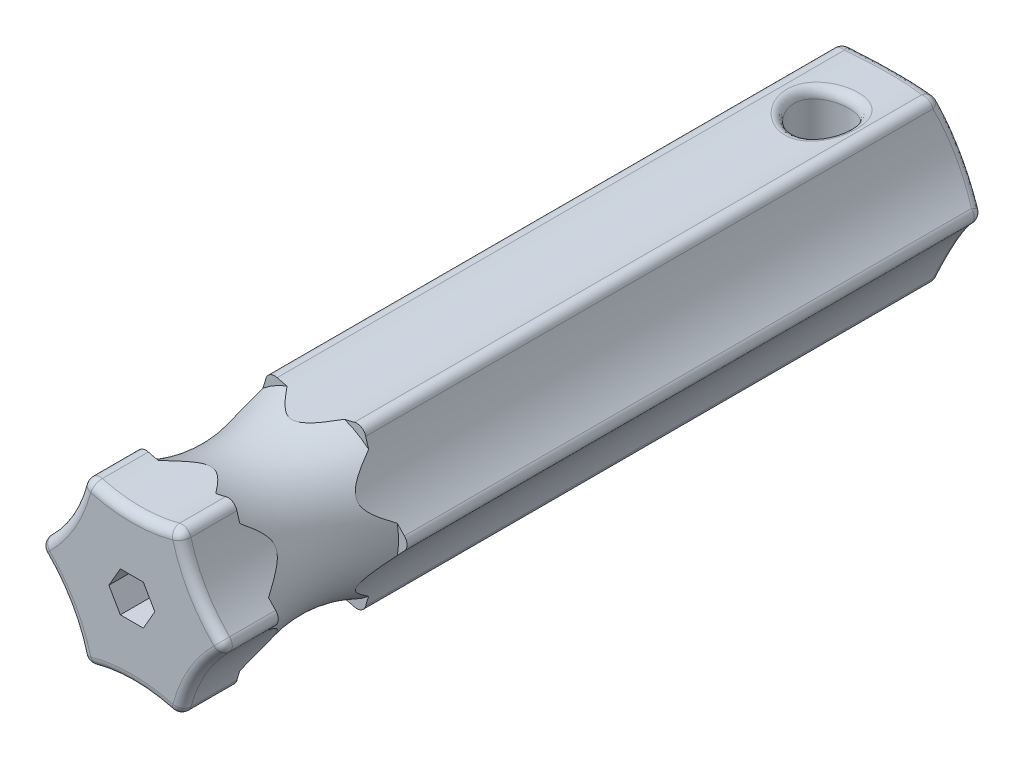
SolidWorks part; units mm, degrees
ref_plane "Alzado" through (0, 0, 0) normal (0, 0, 1) x (1, 0, 0)
ref_plane "Planta" through (0, 0, 0) normal (0, 1, 0) x (1, 0, 0)
ref_plane "Vista lateral" through (0, 0, 0) normal (1, 0, 0) x (0, 0, -1)
sketch "Croquis1" plane through (0, 0, 0) normal (0, 0, 1) x (1, 0, 0)
  line L1 (10.3923, 0) -> (5.1962, 9)
  line L2 (5.1962, 9) -> (-5.1962, 9)
  line L3 (-5.1962, 9) -> (-10.3923, 0)
  line L4 (-10.3923, 0) -> (-5.1962, -9)
  line L5 (-5.1962, -9) -> (5.1962, -9)
  line L6 (5.1962, -9) -> (10.3923, 0)
  circle A0 centre (0, 0) radius 9 construction
  dimension "D1" = 18
extrude "Saliente-Extruir1" add sketch "Croquis1" along normal blind 85
sketch "Croquis2" plane through (0, 0, 0) normal (1, 0, 0) x (0, 0, -1)
  line L0 (-85, -9) -> (0, -9) construction
  line L1 (0, 0) -> (-120.6116, 0) construction
  line L4 (-79, -9) -> (-79, -10.447)
  line L5 (-79, -10.447) -> (-65, -10.447)
  line L6 (-65, -10.447) -> (-65, -9)
  arc A0 (-79, -9) -> (-65, -9) centre (-72, -25.5831) cw
  dimension "D3" = 18
  dimension "D1" = 6
  dimension "D2" = 14
revolve "Cortar-Revolución2" cut sketch "Croquis2" angle 360 about L1
sketch "Croquis3" plane through (0, 0, 0) normal (0, 1, 0) x (1, 0, 0)
  line L2 (0, -0.25) -> (0, 21.7171) construction
  line L3 (-10.3923, -65) -> (-10.3923, 0) construction
  line L5 (0, -0.25) -> (0, 1.427)
  line L6 (0, 1.427) -> (-11.7694, 1.8249)
  arc A0 (0, -0.25) -> (-10.3923, -3) centre (-0.2681, -20.2482) ccw
  arc A1 (-10.3923, -3) -> (-11.7694, 1.8249) centre (137.6107, 41.8508) cw
  dimension "D2" = 20
  dimension "D1" = 3
  dimension "D3" = 0.25
revolve "Cortar-Revolución4" cut sketch "Croquis3" angle 360 about L2
sketch "Croquis4" plane through (0, 0, 85) normal (0, 0, 1) x (1, 0, 0)
  line L1 (2.5, 0) -> (1.25, 2.1651)
  line L2 (1.25, 2.1651) -> (-1.25, 2.1651)
  line L3 (-1.25, 2.1651) -> (-2.5, 0)
  line L4 (-2.5, 0) -> (-1.25, -2.1651)
  line L5 (-1.25, -2.1651) -> (1.25, -2.1651)
  line L6 (1.25, -2.1651) -> (2.5, 0)
  circle A0 centre (0, 0) radius 2.1651 construction
  dimension "D1" = 2.5
extrude "Cortar-Extruir1" cut sketch "Croquis4" against normal blind 25
sketch "Croquis5" plane through (0, 0, 0) normal (0, 0, 1) x (1, 0, 0)
  line L0 (-5.1962, 9) -> (5.1962, 9)
  line L1 (5.1962, 9) -> (10.3923, 0)
  line L2 (10.3923, 0) -> (5.1962, -9)
  line L3 (5.1962, -9) -> (-5.1962, -9)
  line L4 (-5.1962, -9) -> (-10.3923, 0)
  line L5 (-10.3923, 0) -> (-5.1962, 9)
  arc A0 (-5.1962, 9) -> (5.1962, 9) centre (0, 24.1327) ccw
  arc A1 (5.1962, 9) -> (10.3923, 0) centre (20.8996, 12.0664) ccw
  arc A2 (10.3923, 0) -> (5.1962, -9) centre (20.8996, -12.0664) ccw
  arc A3 (5.1962, -9) -> (-5.1962, -9) centre (0, -24.1327) ccw
  arc A4 (-5.1962, -9) -> (-10.3923, 0) centre (-20.8996, -12.0664) ccw
  arc A5 (-10.3923, 0) -> (-5.1962, 9) centre (-20.8996, 12.0664) ccw
  point P3 (0, 0)
  point P23 (0, 0)
  dimension "D1" = 16
  dimension "D2" = 6
extrude "Cortar-Extruir2" cut sketch "Croquis5" along normal up to surface (85 mm away) contours L0 A0 | L1 A1 | L2 A2 | L3 A3 | L4 A4 | L5 A5 region at (-7.4931, 4.3261, 0) region at (0, 8.6523, 0) region at (7.4931, 4.3261, 0) region at (-7.4931, -4.3261, 0) region at (7.4931, -4.3261, 0) region at (0, -8.6523, 0) up to face at (0, 0, 85)
sketch "Croquis7" plane through (0, 0, 0) normal (0, 1, 0) x (1, 0, 0)
  circle A0 centre (0, -10) radius 3
  point P2 (0, 0)
  point P4 (0, -22.9462)
  point P5 (0.2681, -8.0204)
  dimension "D1" = 6
  dimension "D2" = 10
extrude "Cortar-Extruir3" cut sketch "Croquis7" against normal through all both and the other way through all
fillet "Redondeo1" radius 1 26 edges at (1.8265, -8.2373, 1.9927) (8.047, -2.5369, 1.9927) (6.2205, 5.7004, 1.9927) (-1.8265, 8.2373, 1.9927) (-8.047, 2.5369, 1.9927) (-6.2205, -5.7004, 1.9927) (7.0432, 4.0664, 85) (7.0432, -4.0664, 85) (0, -8.1327, 85) (-7.0432, -4.0664, 85) (-7.0432, 4.0664, 85) (0, 8.1327, 85) (-10.3923, 0, 34) (-5.1962, -9, 34) (5.1962, -9, 34) (10.3923, 0, 34) (-5.1962, 9, 34) (5.1962, 9, 34) (0.6313, -8.1452, 7.0672) (-0.6313, 8.1452, 7.0672) (-5.1962, 9, 82) (-10.3923, 0, 82) (-5.1962, -9, 82) (5.1962, -9, 82) (10.3923, 0, 82) (5.1962, 9, 82)
